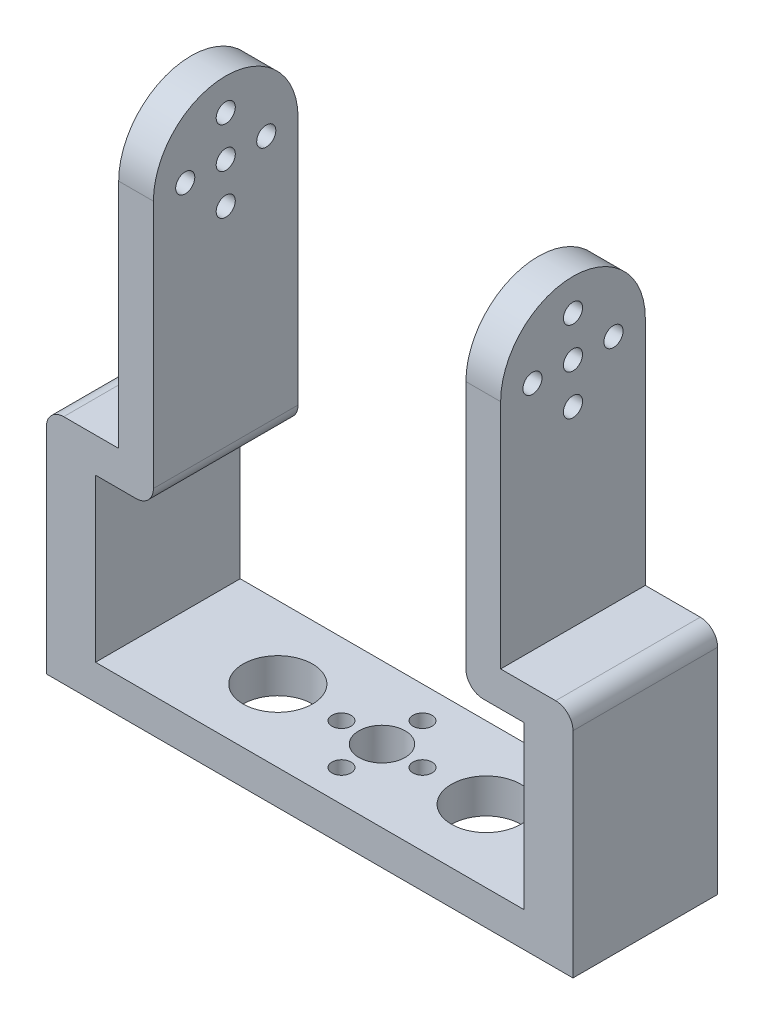
SolidWorks part; units mm, degrees
ref_plane "前视基准面" through (0, 0, 0) normal (0, 0, 1) x (1, 0, 0)
ref_plane "上视基准面" through (0, 0, 0) normal (0, 1, 0) x (1, 0, 0)
ref_plane "右视基准面" through (0, 0, 0) normal (1, 0, 0) x (0, 0, -1)
other "Configuration Table"
sketch "草图1" plane through (0, 0, 0) normal (0, 1, 0) x (1, 0, 0)
  line L1 (-29, -12.5) -> (29, -12.5)
  line L2 (-29, -12.5) -> (-29, 12.5)
  line L3 (-29, 12.5) -> (29, 12.5)
  line L4 (29, -12.5) -> (29, 12.5)
  line L5 (-29, -12.5) -> (29, 12.5) construction
  line L6 (-29, 12.5) -> (29, -12.5) construction
  point P0 (0, 0)
  dimension "D1" = 25
  dimension "D2" = 58
extrude "凸台-拉伸1" add sketch "草图1" along normal blind 6
sketch "草图2" plane through (0, 6, 0) normal (0, 1, 0) x (1, 0, 0)
  line L0 (0, 23.9858) -> (0, -32.3148) construction
  circle A0 centre (0, 0) radius 4
  circle A1 centre (0, 0) radius 7 construction
  circle A2 centre (0, 7) radius 1.65
  circle A3 centre (7, 0) radius 1.65
  circle A4 centre (0, -7) radius 1.65
  circle A5 centre (-7, 0) radius 1.65
  dimension "D1" = 8
  dimension "D2" = 14
  dimension "D3" = 3.3
  dimension "D4" = 4
extrude "切除-拉伸1" cut sketch "草图2" against normal blind 2
sketch "草图3" plane through (29, 0, 0) normal (1, 0, 0) x (0, 0, -1)
  line L0 (12.5, 0) -> (12.5, 80)
  line L2 (0, 0) -> (0, 61.7179) construction
  line L3 (-12.5, 0) -> (12.5, 0) construction
  line L4 (-12.5, 0) -> (-12.5, 80)
  circle A0 centre (0, 80) radius 12.5
  line M4 (-12.5, 0) -> (12.5, 0)
  line M5 (12.5, 0) -> (12.5, 6)
  line M6 (12.5, 6) -> (-12.5, 6)
  line M7 (-12.5, 6) -> (-12.5, 0)
  dimension "D2" = 25
  dimension "D3" = 80
extrude "凸台-拉伸2" add sketch "草图3" against normal blind 2 contours L2 L0 A0 M6 | L2 A0 L4 M6 | A0 L2 | L2 A0 | L2 M4 M6 M7 | L2 M4 M5 M6 region at (29, 3, -6.25) region at (29, 6.7811, -6.25) region at (29, 3, 6.25) region at (29, 80, 0)
sketch "草图4" plane through (29, 0, 0) normal (1, 0, 0) x (0, 0, -1)
  line L0 (0, 53.1577) -> (0, -12.9942) construction
  circle A0 centre (0, 80) radius 7 construction
  circle A1 centre (0, 87) radius 1.65
  circle A2 centre (7, 80) radius 1.65
  circle A3 centre (0, 73) radius 1.65
  circle A4 centre (-7, 80) radius 1.65
  circle A5 centre (0, 80) radius 1.65
  dimension "D1" = 14
  dimension "D2" = 3.3
  dimension "D4" = 3.3
  dimension "D3" = 4
extrude "切除-拉伸2" cut sketch "草图4" against normal blind 2
mirror "镜向1" about plane through (0, 0, 0) normal (1, 0, 0) of "凸台-拉伸2", "切除-拉伸2"
extrude "凸台-拉伸3" add sketch "草图3<3>" along normal blind 4 contours L2 L0 A0 M6 | L2 A0 L4 M6 | A0 | L2 M4 M5 M6 | L2 M4 M6 M7 region at (29, 3, -6.25) region at (29, 6.7811, -6.25) region at (29, 3, 6.25) region at (29, 80, 0)
sketch "草图3<3>" plane through (29, 0, 0) normal (1, 0, 0) x (0, 0, -1) same geometry as "草图3"
sketch "草图5" plane through (-29, 0, 0) normal (-1, 0, 0) x (0, 0, 1)
  line L3 (-12.5, 0) -> (12.5, 0)
  line L4 (12.5, 0) -> (12.5, 80)
  line L5 (-12.5, 80) -> (-12.5, 0)
  line L6 (-12.5, 0) -> (12.5, 0)
  line L7 (12.5, 0) -> (12.5, 80)
  line L8 (-12.5, 80) -> (-12.5, 0)
  circle A0 centre (0, 80) radius 1.65 construction
  arc A1 (12.5, 80) -> (-12.5, 80) centre (0, 80) ccw
  arc A2 (12.5, 80) -> (-12.5, 80) centre (0, 80) ccw
  circle A5 centre (0, 73) radius 1.65 construction
  circle A6 centre (0, 87) radius 1.65 construction
  circle A7 centre (-7, 80) radius 1.65 construction
  circle A8 centre (7, 80) radius 1.65 construction
  circle A9 centre (0, 73) radius 1.65
  circle A10 centre (0, 87) radius 1.65
  circle A11 centre (-7, 80) radius 1.65
  circle A12 centre (0, 80) radius 1.65
  circle A13 centre (7, 80) radius 1.65
  dimension "D1" = 0
extrude "凸台-拉伸4" add sketch "草图5" along normal blind 4
extrude "切除-拉伸3" cut sketch "草图4<2>" along normal blind 6
sketch "草图4<2>" plane through (29, 0, 0) normal (1, 0, 0) x (0, 0, -1) same geometry as "草图4"
extrude "切除-拉伸4" cut sketch "草图2<2>" against normal up to surface (6 mm away) up to face at (0, 0, 0)
sketch "草图2<2>" plane through (0, 6, 0) normal (0, 1, 0) x (1, 0, 0) same geometry as "草图2"
sketch "草图6" plane through (0, 6, 0) normal (0, 1, 0) x (1, 0, 0)
  line L0 (0, 22.4442) -> (0, -18.4386) construction
  line L1 (-52.1828, 0) -> (48.3007, 0) construction
  circle A0 centre (-18, 0) radius 6
  circle A1 centre (18, 0) radius 6
  dimension "D1" = 12
  dimension "D2" = 36
extrude "切除-拉伸5" cut sketch "草图6" against normal up to next
sketch "草图8" plane through (-27, 0, 0) normal (1, 0, 0) x (0, 0, -1)
  line L0 (-12.5, 52) -> (12.5, 52)
  line L1 (-12.5, 0) -> (-12.5, 80) construction
  line L2 (12.5, 0) -> (12.5, 80) construction
  line L3 (12.5, 52) -> (12.5, 46)
  line L4 (12.5, 46) -> (-12.5, 46)
  line L5 (-12.5, 46) -> (-12.5, 52)
  line L6 (-12.5, 6) -> (-12.5, 80) construction
  line L7 (-12.5, 6) -> (12.5, 6) construction
  dimension "D1" = 6
  dimension "D2" = 40
sketch "草图9" plane through (33, 0, 0) normal (1, 0, 0) x (0, 0, -1)
  line L0 (-12.5, 40) -> (12.5, 40)
  line L1 (-12.5, 0) -> (-12.5, 80) construction
  line L2 (12.5, 0) -> (12.5, 80) construction
  line L3 (12.5, 40) -> (12.5, 0)
  line L4 (12.5, 0) -> (-12.5, 0)
  line L5 (-12.5, 0) -> (-12.5, 40)
  dimension "D1" = 40
extrude "凸台-拉伸6" add sketch "草图9" along normal blind 12.5
mirror "镜向2" about plane through (0, 0, 0) normal (1, 0, 0) of "凸台-拉伸6"
sketch "草图10" plane through (27, 0, 0) normal (-1, 0, 0) x (0, 0, 1)
  line L0 (-12.5, 34) -> (12.5, 34)
  line L1 (-12.5, 6) -> (-12.5, 80) construction
  line L2 (12.5, 6) -> (12.5, 80) construction
  line L3 (12.5, 34) -> (12.5, 6)
  line L4 (-12.5, 6) -> (12.5, 6) construction
  line L5 (12.5, 6) -> (-12.5, 6)
  line L6 (-12.5, 6) -> (-12.5, 34)
  dimension "D1" = 6
extrude "切除-拉伸6" cut sketch "草图10" against normal blind 10
mirror "镜向3" about plane through (0, 0, 0) normal (1, 0, 0) of "切除-拉伸6"
fillet "圆角1" radius 3 4 edges at (27, 34, 0) (-27, 34, 0) (-45.5, 40, 0) (45.5, 40, 0)
